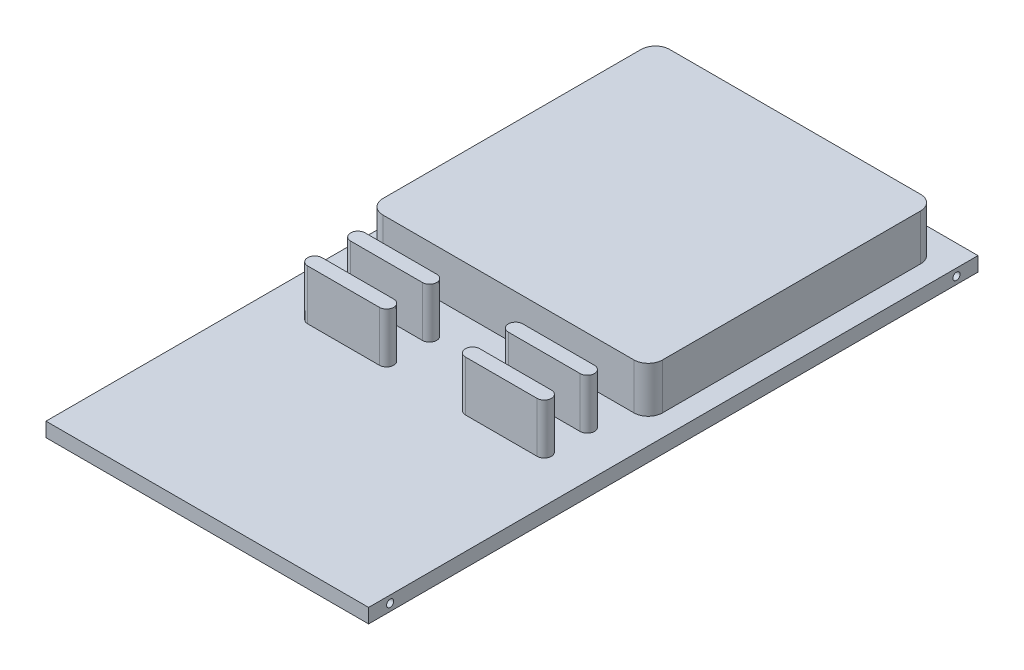
SolidWorks part; units mm, degrees
ref_plane "Front Plane" through (0, 0, 0) normal (0, 0, 1) x (1, 0, 0)
ref_plane "Top Plane" through (0, 0, 0) normal (0, 1, 0) x (1, 0, 0)
ref_plane "Right Plane" through (0, 0, 0) normal (1, 0, 0) x (0, 0, -1)
sketch "Sketch1" plane through (0, 0, 0) normal (0, 1, 0) x (1, 0, 0)
  line L1 (0, 0) -> (57.15, 0)
  line L2 (0, 0) -> (0, 107.95)
  line L3 (0, 107.95) -> (57.15, 107.95)
  line L4 (57.15, 0) -> (57.15, 107.95)
  dimension "D1" = 107.95
  dimension "D2" = 57.15
extrude "Boss-Extrude1" add sketch "Sketch1" along normal blind 2.54
sketch "Sketch2" plane through (0, 2.54, 0) normal (0, 1, 0) x (1, 0, 0)
  line L0 (0, 39.37) -> (57.15, 39.37) construction
  line L1 (0, 107.95) -> (0, 0) construction
  line L2 (57.15, 0) -> (57.15, 107.95) construction
  line L3 (0, 46.99) -> (57.15, 46.99) construction
  line L4 (0, 0) -> (57.15, 0) construction
  line L5 (28.575, 107.95) -> (28.575, 0) construction
  line L6 (57.15, 107.95) -> (0, 107.95) construction
  line L7 (8.255, 39.37) -> (20.955, 39.37) construction
  line L8 (8.255, 40.64) -> (20.955, 40.64)
  line L9 (8.255, 38.1) -> (20.955, 38.1)
  line L10 (48.895, 39.37) -> (36.195, 39.37) construction
  line L11 (48.895, 40.64) -> (36.195, 40.64)
  line L12 (48.895, 38.1) -> (36.195, 38.1)
  line L13 (8.255, 46.99) -> (20.955, 46.99) construction
  line L14 (8.255, 48.26) -> (20.955, 48.26)
  line L15 (8.255, 45.72) -> (20.955, 45.72)
  line L16 (48.895, 46.99) -> (36.195, 46.99) construction
  line L17 (48.895, 48.26) -> (36.195, 48.26)
  line L18 (48.895, 45.72) -> (36.195, 45.72)
  arc A1 (8.255, 40.64) -> (8.255, 38.1) centre (8.255, 39.37) ccw
  arc A2 (20.955, 38.1) -> (20.955, 40.64) centre (20.955, 39.37) ccw
  arc A3 (48.895, 40.64) -> (48.895, 38.1) centre (48.895, 39.37) cw
  arc A4 (36.195, 38.1) -> (36.195, 40.64) centre (36.195, 39.37) cw
  arc A5 (8.255, 48.26) -> (8.255, 45.72) centre (8.255, 46.99) ccw
  arc A6 (20.955, 45.72) -> (20.955, 48.26) centre (20.955, 46.99) ccw
  arc A7 (48.895, 48.26) -> (48.895, 45.72) centre (48.895, 46.99) cw
  arc A8 (36.195, 45.72) -> (36.195, 48.26) centre (36.195, 46.99) cw
  point P18 (14.605, 39.37)
  point P25 (42.545, 39.37)
  point P32 (14.605, 46.99)
  point P39 (42.545, 46.99)
  dimension "D1" = 39.37
  dimension "D3" = 46.99
  dimension "D4" = 14.605
  dimension "D5" = 2.54
  dimension "D6" = 12.7
  dimension "D7" = 14.605
  dimension "D8" = 12.7
  dimension "D9" = 2.54
extrude "Boss-Extrude2" add sketch "Sketch2" along normal blind 8.89
sketch "Sketch3" plane through (0, 0, 0) normal (0, 0, 1) x (1, 0, 0)
  line L0 (0, 0) -> (0, 10.16) construction
  dimension "D1" = 10.16
sketch "Sketch4" plane through (0, 0, 0) normal (-1, 0, 0) x (0, 0, 1)
  line L0 (-107.95, 1.27) -> (0, 1.27) construction
  line L1 (-107.95, 2.54) -> (-107.95, 0) construction
  line L2 (0, 0) -> (0, 10.16) construction
  line L3 (-53.975, 2.54) -> (-53.975, 0) construction
  line L4 (-107.95, 2.54) -> (0, 2.54) construction
  line L5 (-107.95, 0) -> (0, 0) construction
  circle A0 centre (-104.14, 1.27) radius 0.635
  circle A1 centre (-3.81, 1.27) radius 0.635
  dimension "D1" = 1.27
  dimension "D2" = 3.81
extrude "Cut-Extrude1" cut sketch "Sketch4" against normal blind 10.16
ref_plane "Plane1" through (28.575, 0, 0) normal (-1, 0, 0) x (0, 0, 1)
mirror "Mirror1" about plane through (28.575, 0, 0) normal (-1, 0, 0) of "Cut-Extrude1"
sketch "Sketch5" plane through (0, 2.54, 0) normal (0, 1, 0) x (1, 0, 0)
  line L0 (0, 78.74) -> (57.15, 78.74) construction
  line L1 (0, 107.95) -> (0, 0) construction
  line L2 (57.15, 0) -> (57.15, 107.95) construction
  line L3 (57.15, 107.95) -> (0, 107.95) construction
  line L5 (3.81, 53.34) -> (53.34, 53.34)
  line L6 (3.81, 53.34) -> (3.81, 104.14)
  line L7 (3.81, 104.14) -> (53.34, 104.14)
  line L8 (53.34, 53.34) -> (53.34, 104.14)
  line L9 (3.81, 53.34) -> (53.34, 104.14) construction
  line L10 (3.81, 104.14) -> (53.34, 53.34) construction
  point P8 (28.575, 78.74)
  dimension "D2" = 3.81
  dimension "D1" = 29.21
  dimension "D3" = 3.81
extrude "Boss-Extrude3" add sketch "Sketch5" along normal blind 8.128
fillet "Fillet1" radius 2.54 4 edges at (53.34, 6.604, -53.34) (53.34, 6.604, -104.14) (3.81, 6.604, -104.14) (3.81, 6.604, -53.34)
